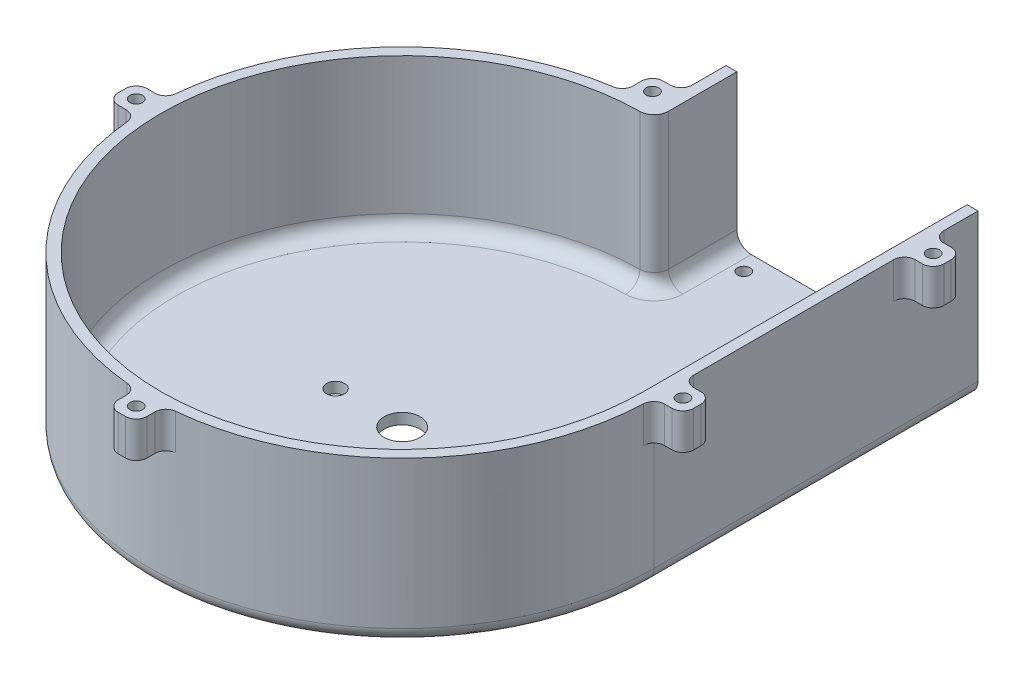
SolidWorks part; units mm, degrees
ref_plane "Front Plane" through (0, 0, 0) normal (0, 0, 1) x (1, 0, 0)
ref_plane "Top Plane" through (0, 0, 0) normal (0, 1, 0) x (1, 0, 0)
ref_plane "Right Plane" through (0, 0, 0) normal (1, 0, 0) x (0, 0, -1)
sketch "Sketch2" plane through (0, 0, 0) normal (0, 1, 0) x (1, 0, 0)
  line L0 (0, 70) -> (70, 70) construction
  line L2 (70, 0) -> (70, 90)
  line L3 (70, 90) -> (0, 90)
  line L4 (0, 70) -> (0, 90)
  circle A0 centre (0, 0) radius 59 construction
  arc A1 (0, 70) -> (70, 0) centre (0, 0) ccw
  circle A2 centre (0, 0) radius 18.5 construction
  circle A3 centre (18.5, 0) radius 2.5
  circle A4 centre (-18.5, 0) radius 2.5
  circle A5 centre (0, 0) radius 5
  dimension "D1" = 118
  dimension "D2" = 70
  dimension "D4" = 5
  dimension "D6" = 10
  dimension "D5" = 37
  dimension "D7" = 20
extrude "Boss-Extrude1" add sketch "Sketch2" along normal blind 3
sketch "Sketch3" plane through (0, 3, 0) normal (0, 1, 0) x (1, 0, 0)
  line L3 (70, 90) -> (0, 90) construction
  line L4 (0, 90) -> (3, 90)
  line L5 (67, 90) -> (70, 90)
  line L6 (67, 0) -> (67, 87)
  line L7 (67, 87) -> (3, 87)
  line L8 (3, 87) -> (3, 66.9328)
  line L9 (67, 0) -> (67, 90)
  line L11 (3, 90) -> (3, 66.9328)
  line L12 (70, 0) -> (70, 90)
  line L13 (70, 90) -> (0, 90)
  line L14 (0, 90) -> (0, 70)
  line L15 (70, 0) -> (70, 90)
  line L17 (0, 90) -> (0, 70)
  arc A2 (3, 66.9328) -> (67, 0) centre (0, 0) ccw
  arc A3 (3, 66.9328) -> (67, 0) centre (0, 0) ccw
  arc A4 (0, 70) -> (70, 0) centre (0, 0) ccw
  arc A5 (0, 70) -> (70, 0) centre (0, 0) ccw
  dimension "D1" = 3
  dimension "D2" = 0
extrude "Boss-Extrude2" add sketch "Sketch3" along normal blind 42
sketch "Sketch4" plane through (0, 45, 0) normal (0, 1, 0) x (1, 0, 0)
  line L0 (-4, 77.5414) -> (-4, 69.5414) construction
  line L1 (0, 77.5414) -> (-8, 77.5414)
  line L2 (0, 77.5414) -> (0, 70)
  line L4 (-8, 77.5414) -> (-8, 69.5414)
  line L5 (70, 77.5414) -> (78, 77.5414)
  line L6 (70, 77.5414) -> (70, 69.5414)
  line L7 (70, 69.5414) -> (78, 69.5414)
  line L8 (78, 77.5414) -> (78, 69.5414)
  line L9 (74, 77.5414) -> (74, 69.5414) construction
  line L10 (0, 70) -> (0, 69.5414) construction
  line L11 (0, 69.5414) -> (-8, 69.5414) construction
  line L13 (70, 0) -> (70, 90) construction
  line L14 (-77.8856, 0) -> (-69.8856, 0) construction
  line L15 (-69.8856, 4) -> (-77.8856, 4)
  line L16 (-69.8856, 4) -> (-69.8856, -4)
  line L17 (-69.8856, -4) -> (-77.8856, -4)
  line L18 (-77.8856, 4) -> (-77.8856, -4)
  line L19 (0, -69.8856) -> (0, -77.8856) construction
  line L20 (-4, -69.8856) -> (4, -69.8856)
  line L21 (-4, -69.8856) -> (-4, -77.8856)
  line L22 (-4, -77.8856) -> (4, -77.8856)
  line L23 (4, -69.8856) -> (4, -77.8856)
  line L24 (78, 4) -> (70, 4) construction
  line L25 (70, 0) -> (78, 0)
  line L26 (70, 0) -> (70, 8)
  line L27 (70, 8) -> (78, 8)
  line L28 (78, 0) -> (78, 8)
  circle A0 centre (-4, 73.5414) radius 1.75
  circle A1 centre (74, 73.5414) radius 1.75
  arc A2 (0, 70) -> (70, 0) centre (0, 0) ccw construction
  circle A3 centre (-73.8856, 0) radius 1.75
  circle A4 centre (0, -73.8856) radius 1.75
  circle A5 centre (74, 4) radius 1.75
  arc M8 (0, 70) -> (70, 0) centre (0, 0) ccw
  line M9 (70, 0) -> (70, 90)
  line M15 (0, 90) -> (0, 70)
  dimension "D5" = 3.5
  dimension "D6" = 3.5
  dimension "D8" = 3.5
  dimension "D10" = 3.5
  dimension "D12" = 3.5
  dimension "D1" = 8
  dimension "D2" = 8
  dimension "D3" = 8
  dimension "D4" = 8
  dimension "D7" = 8
  dimension "D9" = 8
  dimension "D11" = 8
extrude "Boss-Extrude3" add sketch "Sketch4" against normal blind 10 contours L23 L21 L22 A4 M8 | L15 L18 L17 A3 M8 | L25 L28 L27 A5 M9 | L8 L5 L7 A1 M9 | L1 L4 A0 M8 M15 region at (-0.1131, 45, -73.7707) region at (70.1131, 45, -73.5414) region at (70.1131, 45, -4) region at (0, 45, 70.1131) region at (-70.1131, 45, 0)
fillet "Fillet1" radius 3 19 edges at (70, 40, -77.5414) (78, 40, -77.5414) (78, 40, -69.5414) (70, 40, -69.5414) (70, 40, -8) (78, 40, -8) (78, 40, 0) (70, 40, 0) (4, 40, 69.8856) (4, 40, 77.8856) (-4, 40, 77.8856) (-4, 40, 69.8856) (-69.8856, 40, 4) (-77.8856, 40, 4) (-77.8856, 40, -4) (-69.8856, 40, -4) (-8, 40, -69.5414) (0, 40, -77.5414) (-8, 40, -77.5414)
fillet "Fillet2" radius 4 1 edges at (3, 24, -66.9328)
fillet "Fillet3" radius 4 4 edges at (67, 3, -45) (3, 3, -80.4965) (1.8483, 3, -68.1845) (-47.0413, 3, 47.7086)
fillet "Fillet4" radius 4 4 edges at (-49.4975, 0, 49.4975) (70, 0, -45) (0, 17.5, -70) (0, 0, -80)
sketch "Sketch5" plane through (0, 0, 0) normal (0, -1, 0) x (1, 0, 0)
  line L0 (0, -84.93) -> (70, -84.93) construction
  line L1 (0, -90) -> (0, -73.8918) construction
  line L2 (70, 0) -> (70, -90) construction
  line L3 (66, -90) -> (4, -90) construction
  circle A0 centre (10, -84.93) radius 1.75
  circle A1 centre (60, -84.93) radius 1.75
  dimension "D2" = 3.5
  dimension "D3" = 3.5
  dimension "D1" = 5.07
  dimension "D4" = 10
  dimension "D5" = 10
extrude "Cut-Extrude1" cut sketch "Sketch5" against normal through all
